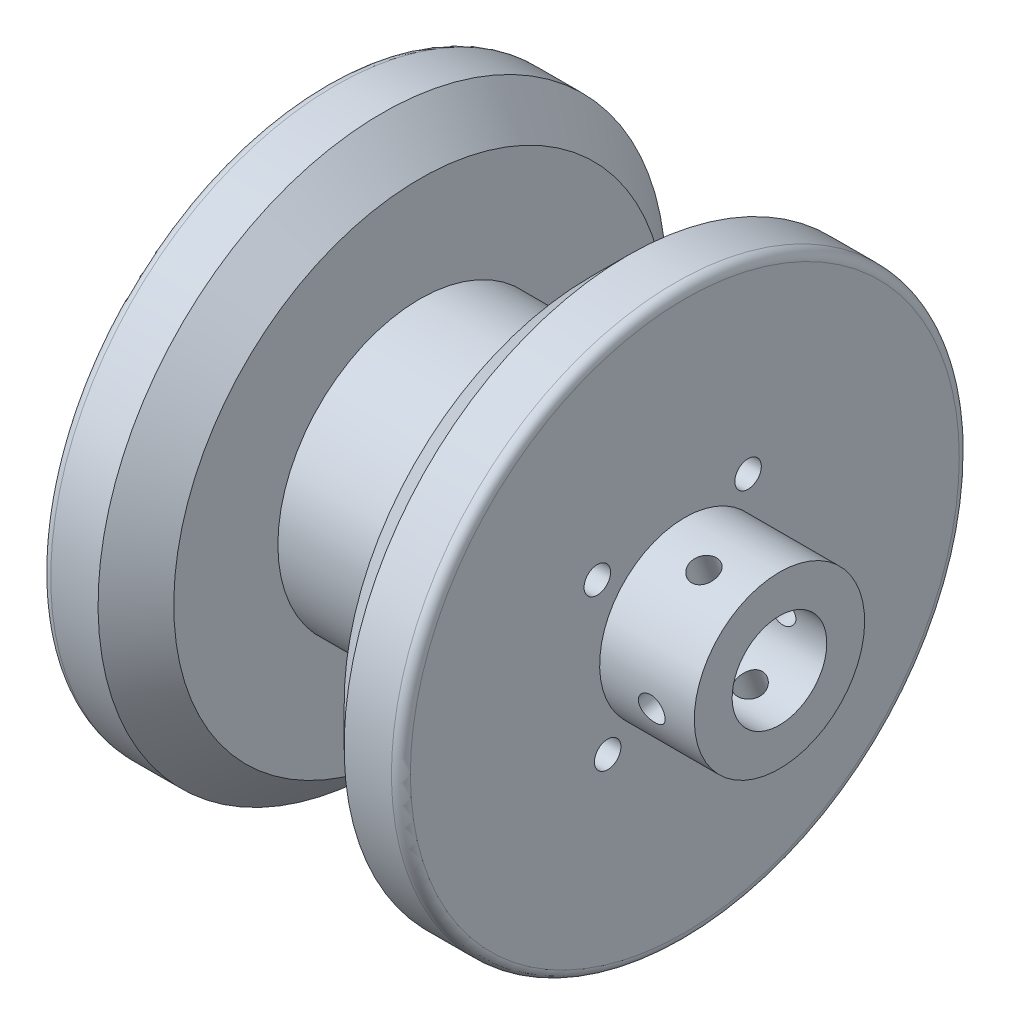
SolidWorks part; units mm, degrees
ref_plane "Front Plane" through (0, 0, 0) normal (0, 0, 1) x (1, 0, 0)
ref_plane "Top Plane" through (0, 0, 0) normal (0, 1, 0) x (1, 0, 0)
ref_plane "Right Plane" through (0, 0, 0) normal (1, 0, 0) x (0, 0, -1)
sketch "Sketch1" plane through (0, 0, 0) normal (0, 0, 1) x (1, 0, 0)
  line L0 (-19, 0) -> (19, 0)
  line L1 (19, 0) -> (19, 30)
  line L2 (19, 30) -> (9, 30)
  line L3 (9, 30) -> (9, 15)
  line L4 (9, 15) -> (-9, 15)
  line L5 (-9, 15) -> (-9, 30)
  line L6 (-9, 30) -> (-19, 30)
  line L7 (-19, 30) -> (-19, 0)
  point P10 (0, 0)
  point P13 (0, 15)
  dimension "D1" = 10
  dimension "D2" = 18
  dimension "D3" = 30
  dimension "D4" = 15
revolve "Revolve1" add sketch "Sketch1" angle 360 about L0
fillet "Fillet1" [suppressed] radius 4
fillet "Fillet2" [suppressed] radius 2
sketch "Sketch2" plane through (19, 0, 0) normal (1, 0, 0) x (0, 0, -1)
  circle A0 centre (0, 0) radius 9
  dimension "D1" = 18
extrude "Boss-Extrude1" add sketch "Sketch2" along normal blind 10
fillet "Fillet3" [suppressed] radius 3
sketch "Sketch3" plane through (29, 0, 0) normal (1, 0, 0) x (0, 0, -1)
  circle A0 centre (0, 0) radius 5
  dimension "D1" = 10
extrude "Cut-Extrude1" cut sketch "Sketch3" against normal through all
hole_wizard "Ø1.0mm Dowel Hole1" positions "3DSketch1" profile "Sketch4" hole size "Ø1.0" standard "ANSI Metric"
sketch3d "3DSketch1"
  point P0 (24.1787, 8.421, 3.1759)
  point P2 (24.3919, 1.4216, -8.887)
sketch "Sketch4" plane through (24.1787, 8.421, 3.1759) normal (1, 0, 0) x (0, -0.3529, 0.9357)
  line L0 (0, 0) -> (0, 34)
  line L1 (0, 34) -> (1.4, 33.1588)
  line L2 (1.4, 33.1588) -> (1.4, 0)
  line L5 (1.4, 0) -> (0, 0)
  line L10 (0, 34) -> (-1.4, 33.1588) construction
  line L11 (0, -6.35) -> (0, 107.95) construction
  dimension "Hole Dia." = 2.8
  dimension "Hole Depth" = 34
  dimension "Drill Angle" = 118
chamfer "Chamfer1" distance 4 angle 45 2 edges at (9, -30, 0) (-9, -30, 0)
fillet "Fillet4" radius 1 2 edges at (19, -30, 0) (-19, -30, 0)
sketch "Sketch5" plane through (0, 0, 0) normal (0, 0, 1) x (1, 0, 0)
  line L1 (8.9, -29.0567) -> (9, -29.0567)
  line L2 (8.9, -29.0567) -> (8.9, 25.4884)
  line L3 (8.9, 25.4884) -> (9, 25.4884)
  line L4 (9, -29.0567) -> (9, 25.4884)
  dimension "D1" = 0.1
extrude "Cut-Extrude2" cut sketch "Sketch5" against normal through all both and the other way through all
sketch "Sketch6" plane through (19, 0, 0) normal (1, 0, 0) x (0, 0, -1)
  circle A0 centre (0, 0) radius 15 construction
  circle A1 centre (0, 0) radius 15
  point P3 (-8.5562, 8.453)
  point P4 (9.4939, 8.453)
  point P5 (-8.5562, -9.139)
  point P6 (9.4939, -9.139)
hole_wizard "Ø1.0mm Dowel Hole2" positions "3DSketch2" profile "Sketch7" hole size "Ø1.0" standard "ANSI Metric"
sketch3d "3DSketch2"
  point P0 (19, 9.6436, -6.6826)
  point P2 (19, -8.1588, -8.6955)
  point P4 (19, -8.6015, 8.1502)
  point P6 (19, 7.916, 9.2468)
sketch "Sketch7" plane through (19, 9.6436, -6.6826) normal (0, 1, 0) x (0, 0, -1)
  line L0 (0, 0) -> (0, 20)
  line L1 (0, 20) -> (1.4, 19.1588)
  line L2 (1.4, 19.1588) -> (1.4, 0)
  line L5 (1.4, 0) -> (0, 0)
  line L10 (0, 20) -> (-1.4, 19.1588) construction
  line L11 (0, -6.35) -> (0, 107.95) construction
  dimension "Hole Dia." = 2.8
  dimension "Hole Depth" = 20
  dimension "Drill Angle" = 118
